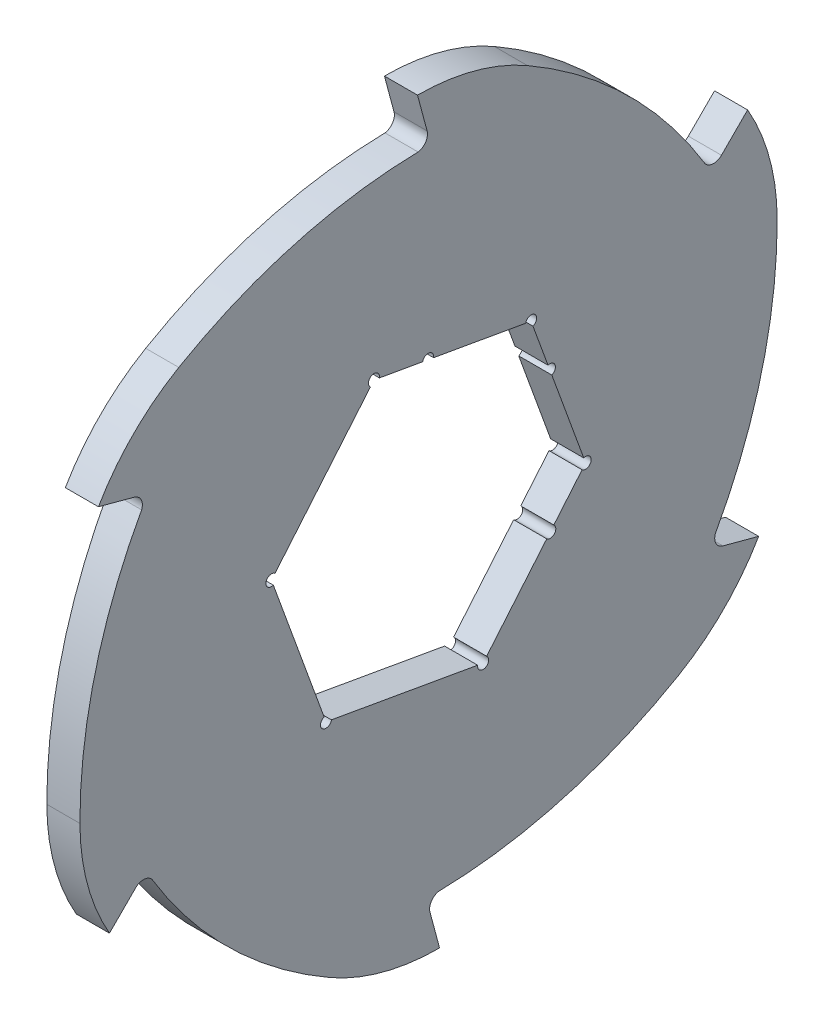
SolidWorks part; units mm, degrees
note: '?' marks a value the reader was unsure of.
material "1.0037 (S235JR)"
ref_plane "Alzado" through (0, 0, 0) normal (0, 0, 1) x (1, 0, 0)
ref_plane "Planta" through (0, 0, 0) normal (0, 1, 0) x (1, 0, 0)
ref_plane "Vista lateral" through (0, 0, 0) normal (1, 0, 0) x (0, 0, -1)
sketch "Sketch1" plane through (0, 0, 0) normal (1, 0, 0) x (0, 0, -1)
  line L0 (-56.6126, 0) -> (65.57, 0) construction
  line L1 (18.5928, 22.158) -> (-9.893, 27.1808)
  line L2 (-9.893, 27.1808) -> (-28.4858, 5.0228)
  line L3 (-28.4858, 5.0228) -> (-18.5928, -22.158)
  line L4 (-18.5928, -22.158) -> (9.893, -27.1808)
  line L5 (9.893, -27.1808) -> (28.4858, -5.0228)
  line L6 (28.4858, -5.0228) -> (18.5928, 22.158)
  circle A0 centre (0, 0) radius 25.05 construction
  circle A1 centre (0, 0) radius 59
  dimension "D2" = 118
  dimension "D1" = 50.1
  dimension "D3" = 10
extrude "Extrude1" add sketch "Sketch1" along normal mid plane 6
ref_axis "Axis1" through (-5.5, 0, 0) along (1, 0, 0)?
sketch "Sketch2" plane through (0, 0, 0) normal (1, 0, 0) x (0, 0, -1)
  line L0 (-2, 67.9618) -> (-0.2627, 61.4781)
  line L1 (0, 0) -> (0, 77.6328) construction
  line L4 (-2.1226, 58.9618) -> (0, 0) construction
  circle A0 centre (0, 0) radius 59 construction
  arc A1 (-2, 67.9618) -> (17.9271, 62.6448) centre (-2, 27.9618) cw
  arc A3 (51.2137, 29.2943) -> (-2.1226, 58.9618) centre (0, 0) ccw
  arc A4 (-0.2627, 61.4781) -> (-2.1226, 58.9618) centre (-2.1946, 60.9605) cw
  arc A5 (17.9271, 62.6448) -> (51.2137, 29.2943) centre (-26.9089, -15.3919) cw
  point P10 (-2, 67.9618)
  dimension "D2" = 40
  dimension "D4" = 2
  dimension "D3" = 9
  dimension "D6" = 90
  dimension "D1" = 15
  dimension "D5" = 2
extrude "Extrude2" add sketch "Sketch2" against normal mid plane 6
fillet "Fillet1" [suppressed] radius 0.6
pattern_circular "CirPattern1" count 6 over 360 about axis through (0, 0, 0) along (1, 0, 0) of "Extrude2", "Fillet1"
sketch "Sketch4" [suppressed] plane through (3, 0, 0) normal (1, 0, 0) x (0, 0, -1)
  circle A0 centre (0, 0) radius 67.9646 construction
  dimension "D1" = 135.9291
hole_wizard "Ø2.0 (2) Diameter Hole1" positions "Sketch5" profile "Sketch7" hole size "Ø2.0" standard "ISO" end condition up to next
sketch "Sketch5" plane through (3, 0, 0) normal (1, 0, 0) x (0, 0, -1)
  point P0 (-9.893, 27.1808)
  point P7 (18.5928, 22.158)
  point P8 (28.4858, -5.0228)
  point P9 (9.893, -27.1808)
  point P10 (-18.5928, -22.158)
  point P11 (-28.4858, 5.0228)
  dimension "D1" = 6
sketch "Sketch7" plane through (3, 27.1808, 9.893) normal (0, 1, 0) x (0, 0, -1)
  line L0 (0, 0) -> (0, 6)
  line L1 (0, 6) -> (1, 6)
  line L2 (1, 6) -> (1, 0)
  line L5 (1, 0) -> (0, 0)
  line L11 (0, -6.35) -> (0, 107.95) construction
  dimension "Diámetro de taladro hasta el siguiente" = 2
  dimension "Profundidad de taladro hasta el siguiente" = 6
hole_wizard "Ø2.0 (2) Diameter Hole3" positions "Sketch10" profile "Sketch11" hole size "Ø2.0" standard "ISO" end condition up to next
sketch "Sketch10" plane through (3, 0, 0) normal (1, 0, 0) x (0, 0, -1)
  line L0 (-8.9082, 27.0072) -> (-0.0695, 25.4487) construction
  line L1 (17.608, 22.3317) -> (-8.9082, 27.0072) construction
  line L2 (-0.0695, 25.4487) -> (8.7693, 23.8902) construction
  line L3 (8.7693, 23.8902) -> (17.608, 22.3317) construction
  point P2 (-0.0695, 25.4487)
sketch "Sketch11" plane through (3, 25.4487, 0.0695) normal (0, 1, 0) x (0, 0, -1)
  line L0 (0, 0) -> (0, 6.001)
  line L1 (0, 6.001) -> (1, 6.001)
  line L2 (1, 6.001) -> (1, 0)
  line L5 (1, 0) -> (0, 0)
  line L11 (0, -6.35) -> (0, 107.95) construction
  dimension "Diámetro de taladro hasta el siguiente" = 2
  dimension "Profundidad de taladro hasta el siguiente" = 6.001
hole_wizard "Ø2.0 (2) Diameter Hole4" [suppressed] positions "Sketch12" profile "Sketch13" hole size "Ø2.0" standard "ISO"
sketch "Sketch12" plane through (3, 0, 0) normal (1, 0, 0) x (0, 0, -1)
  line L0 (13.4626, 25.05) -> (-3.4875, 25.05) construction
  point P0 (4.9875, 25.05)
sketch "Sketch13" plane through (3, 25.05, -4.9875) normal (0, 1, 0) x (0, 0, -1)
  line L0 (0, 0) -> (0, 6)
  line L1 (0, 6) -> (1, 6)
  line L2 (1, 6) -> (1, 0)
  line L5 (1, 0) -> (0, 0)
  line L11 (0, -6.35) -> (0, 107.95) construction
  dimension "Diámetro de taladro hasta el siguiente" = 2
  dimension "Profundidad de taladro hasta el siguiente" = 6
pattern_circular "CirPattern2" count 3 every 60 about axis through (0, 0, 0) along (1, 0, 0) of "Ø2.0 (2) Diameter Hole3"
pattern_circular "CirPattern3" [suppressed] count 1 every? 60? about axis through (-5.5, 0, 0) along (1, 0, 0)
equation "\"D1@Extrude2\"=\"D1@Extrude1\""
